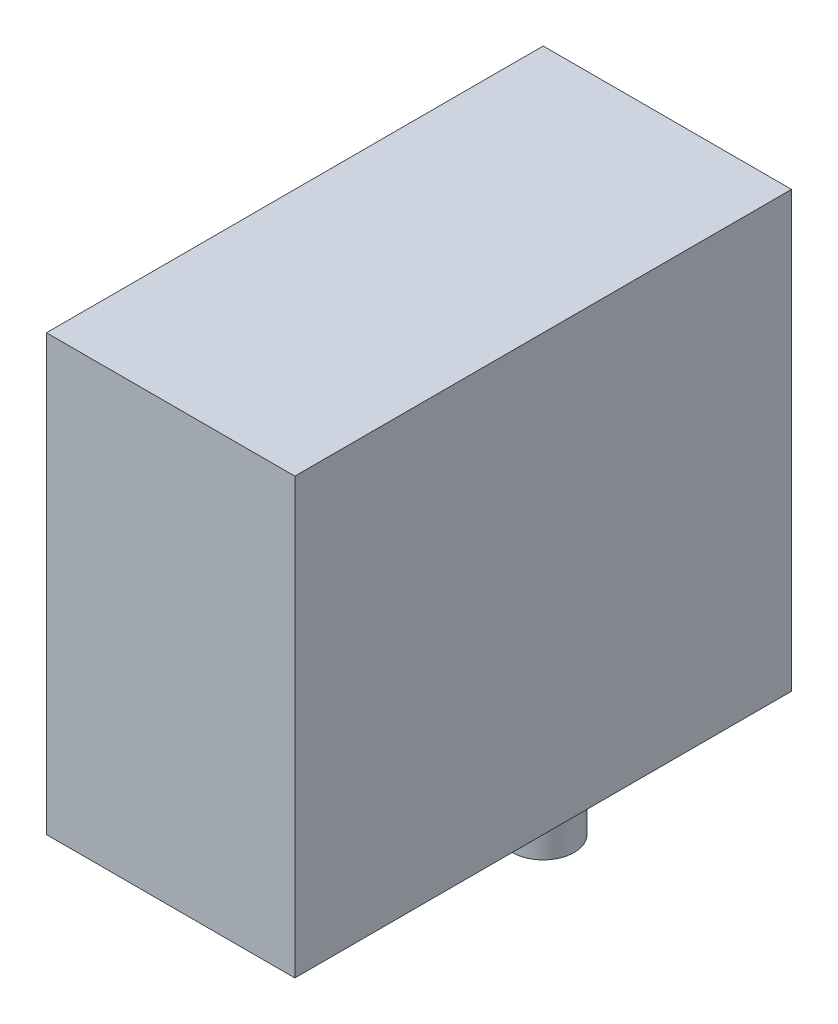
SolidWorks part; units mm, degrees
ref_plane "Front Plane" through (0, 0, 0) normal (0, 0, 1) x (1, 0, 0)
ref_plane "Top Plane" through (0, 0, 0) normal (0, 1, 0) x (1, 0, 0)
ref_plane "Right Plane" through (0, 0, 0) normal (1, 0, 0) x (0, 0, -1)
sketch "Sketch1" plane through (0, 0, 0) normal (0, 1, 0) x (1, 0, 0)
  circle A0 centre (0, 0) radius 2.5
  dimension "D1" = 5
extrude "Boss-Extrude1" add sketch "Sketch1" along normal blind 10
sketch "Sketch3" plane through (0, 10, 0) normal (0, 1, 0) x (1, 0, 0)
  line L1 (10, 10) -> (-10, 10)
  line L2 (10, 10) -> (10, -30)
  line L3 (10, -30) -> (-10, -30)
  line L4 (-10, 10) -> (-10, -30)
  circle A0 centre (0, 0) radius 2.5 construction
  dimension "D3" = 10
  dimension "D1" = 20
  dimension "D2" = 40
  dimension "D4" = 10
extrude "Boss-Extrude2" add sketch "Sketch3" along normal blind 35
ref_axis "Axis1" through (0, 0, 0) along (0, -1, 0)
